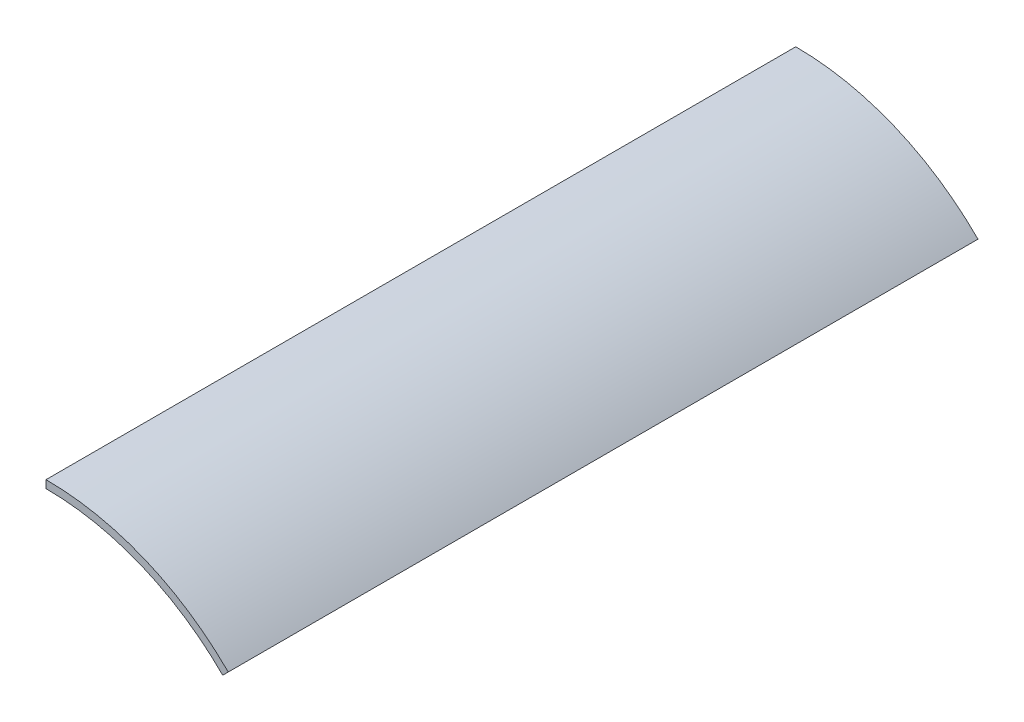
SolidWorks part; units mm, degrees
material "1060 Alloy"
ref_plane "Front Plane" through (0, 0, 0) normal (0, 0, 1) x (1, 0, 0)
ref_plane "Top Plane" through (0, 0, 0) normal (0, 1, 0) x (1, 0, 0)
ref_plane "Right Plane" through (0, 0, 0) normal (1, 0, 0) x (0, 0, -1)
sketch "Sketch1" plane through (0, 0, 0) normal (0, 0, 1) x (1, 0, 0)
  line L0 (0, 104.775) -> (0, 101.6)
  line L1 (74.0871, 74.0871) -> (71.842, 71.842)
  arc A0 (0, 101.6) -> (71.842, 71.842) centre (0, 0) cw
  arc A1 (0, 104.775) -> (74.0871, 74.0871) centre (0, 0) cw
  dimension "D1" = 101.6
  dimension "D4" = 3.175
  dimension "D2" = 3.175
  dimension "D3" = 3.175
  dimension "D5" = 45
extrude "Boss-Extrude1" add sketch "Sketch1" along normal blind 152.4 and the other way blind 152.4
ref_axis "Axis1" through (40.0957, 96.7995, -152.4) along (0, 0, 1)
ref_axis "Axis2" through (38.8806, 93.8662, 152.4) along (0, 0, -1)
ref_plane "Plane1" through (0, 0, 0) normal (0.9239, -0.3827, 0) x (0, 0, -1)
ref_plane "Plane2" through (38.8806, 93.8662, 0) normal (-0.3827, -0.9239, 0) x (0, 0, -1)
